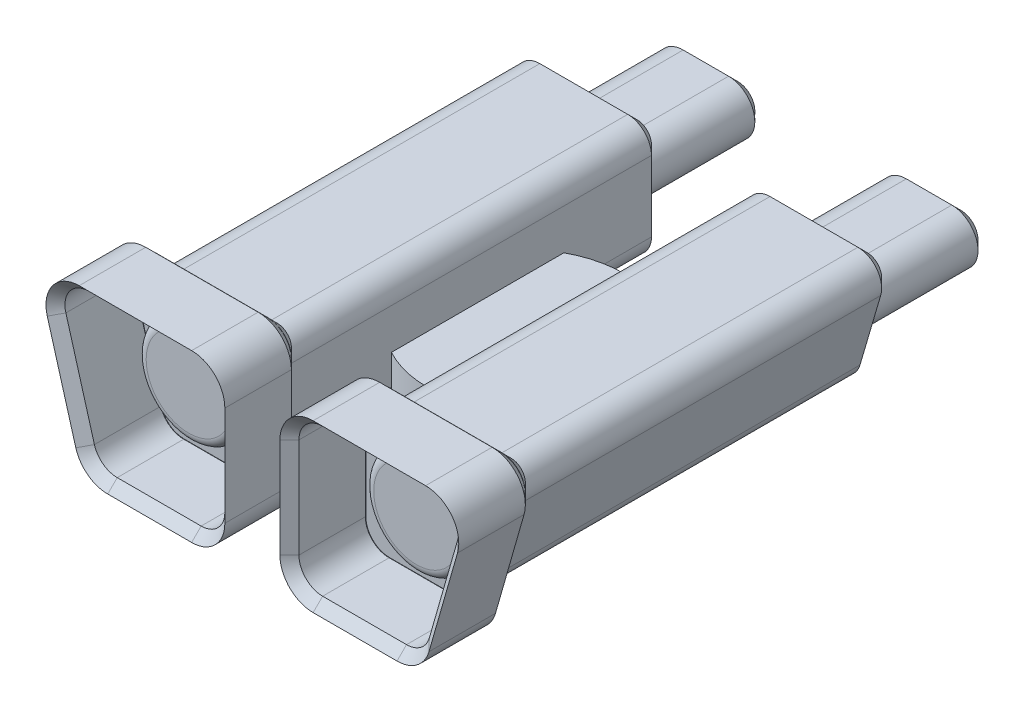
SolidWorks part; units mm, degrees
ref_plane "Front Plane" through (0, 0, 0) normal (0, 0, 1) x (1, 0, 0)
ref_plane "Top Plane" through (0, 0, 0) normal (0, 1, 0) x (1, 0, 0)
ref_plane "Right Plane" through (0, 0, 0) normal (1, 0, 0) x (0, 0, -1)
sketch "Sketch1" plane through (0, 0, 0) normal (0, 0, 1) x (1, 0, 0)
  line L0 (-12.594, 16.7008) -> (88.9795, 16.7008)
  line L1 (88.9795, 16.7008) -> (88.9795, -72.2787)
  line L2 (88.9795, -72.2787) -> (12.8678, -72.2787)
  line L3 (12.8678, -72.2787) -> (-12.594, 16.7008)
extrude "Boss-Extrude1" add sketch "Sketch1" along normal blind 50.8
fillet "Fillet1" radius 17.78 4 edges at (88.9795, -72.2787, 25.4) (88.9795, 16.7008, 25.4) (12.8678, -72.2787, 25.4) (-12.594, 16.7008, 25.4)
shell "Shell2" thickness 5.08 removed face at (45.0312, -28.837, 50.8)
sketch "Sketch2" plane through (0, 0, 5.08) normal (0, 0, 1) x (1, 0, 0)
  line L0 (78.329, 3.9302) -> (1.6012, 3.9302)
  line L1 (1.6012, 3.9302) -> (20.1563, -59.2574)
  line L2 (20.1563, -59.2574) -> (78.329, -59.2574)
  line L3 (78.329, -59.2574) -> (78.329, 3.9302)
extrude "Boss-Extrude3" add sketch "Sketch2" against normal blind 203.2 contours L3 L0 L1 L2
fillet "Fillet2" radius 12.7 4 edges at (20.1563, -59.2574, -99.06) (1.6012, 3.9302, -99.06) (78.329, -59.2574, -99.06) (78.329, 3.9302, -99.06)
sketch "Sketch3" plane through (0, 0, 0) normal (0, 0, -1) x (-1, 0, 0)
  circle A0 centre (-42.8099, -26.4195) radius 27.8701
extrude "Boss-Extrude4" add sketch "Sketch3" against normal blind 19.05
fillet "Fillet4" radius 5.08 1 edges at (14.9398, -26.4195, 19.05)
sketch "Sketch7" plane through (0, 0, -198.12) normal (0, 0, -1) x (-1, 0, 0)
  line L0 (-56.1381, -28.9173) -> (-31.8159, -28.9173) construction
  line L1 (-56.1381, -14.8756) -> (-31.8159, -14.8756)
  line L2 (-56.1381, -42.959) -> (-31.8159, -42.959)
  arc A0 (-56.1381, -14.8756) -> (-56.1381, -42.959) centre (-56.1381, -28.9173) ccw
  arc A1 (-31.8159, -42.959) -> (-31.8159, -14.8756) centre (-31.8159, -28.9173) ccw
  point P2 (-43.977, -28.9173)
extrude "Boss-Extrude5" add sketch "Sketch7" along normal blind 63.5
chamfer "Chamfer2" distance 10 angle 45 8 edges at (80.1797, -63.479, 50.8) (83.8995, -27.789, 50.8) (80.1797, 7.901, 50.8) (41.0935, 11.6208, 50.8) (0.8468, 6.5666, 50.8) (6.4206, -31.2829, 50.8) (18.6278, -64.6393, 50.8) (48.7365, -67.1987, 50.8)
chamfer "Chamfer3" distance 4.92 angle 45 4 edges at (43.977, -14.8756, -261.62) (17.7742, -28.9173, -261.62) (43.977, -42.959, -261.62) (70.1798, -28.9173, -261.62)
chamfer "Chamfer4" distance 4.92 angle 45 8 edges at (74.6092, -55.5377, -198.12) (47.6461, -59.2574, -198.12) (78.329, -27.6636, -198.12) (22.0525, -56.7244, -198.12) (74.6092, 0.2104, -198.12) (11.9295, -31.2419, -198.12) (42.0979, 3.9302, -198.12) (8.3999, -1.1591, -198.12)
chamfer "Chamfer5" distance 10.254 angle 45 8 edges at (48.7365, -72.2787, 0) (83.7718, -67.0711, 0) (15.5695, -68.6955, 0) (88.9795, -27.789, 0) (1.5366, -32.6805, 0) (83.7718, 11.4931, 0) (-3.2094, 9.6249, 0) (41.0935, 16.7008, 0)
ref_plane "Plane1" through (103.729, 0, 0) normal (1, 0, 0) x (0, 0, -1)
mirror "Mirror1" about plane through (103.729, 0, 0) normal (1, 0, 0) of bodies 105
ref_plane "Plane2" through (0, -33.02, 0) normal (0, 1, 0) x (1, 0, 0)
sketch "Sketch9" plane through (0, -33.02, 0) normal (0, 1, 0) x (1, 0, 0)
  line L0 (103.729, -20.7832) -> (103.729, 20.7832) construction
  circle A0 centre (103.729, 100.1345) radius 52.6655
extrude "Boss-Extrude6" add sketch "Sketch9" along normal blind 2.54 and the other way blind 45.72 contours A0
sketch "Sketch13" plane through (0, -78.74, 0) normal (0, -1, 0) x (1, 0, 0)
  line L0 (103.729, -20.7832) -> (103.729, 20.7832) construction
  circle A1 centre (103.729, -101.0446) radius 12.7
extrude "Cut-Extrude3" cut sketch "Sketch13" against normal blind 25.4
